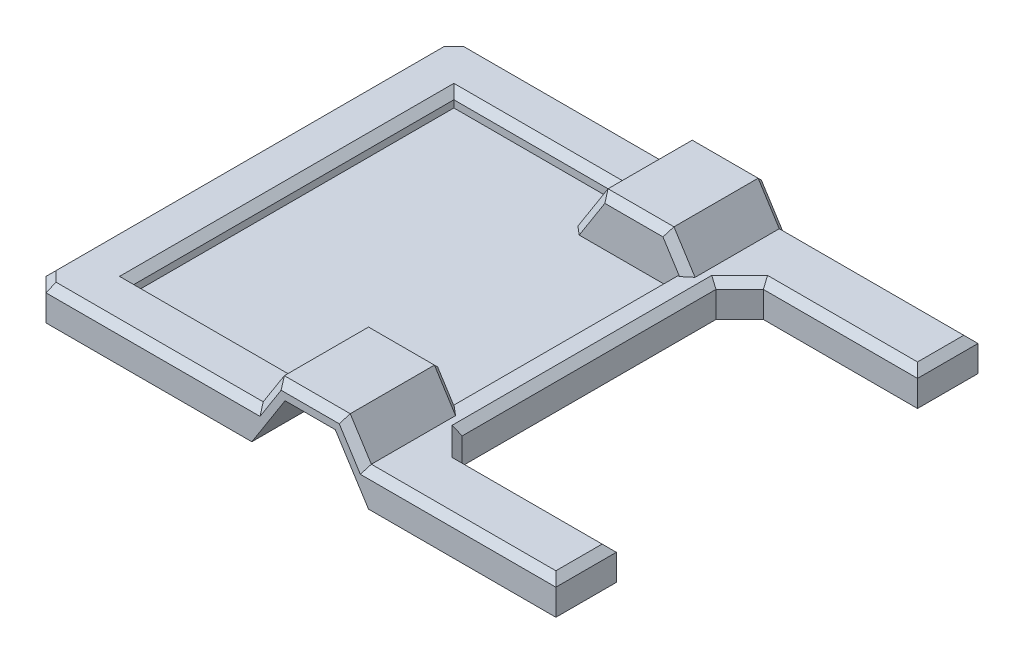
SolidWorks part; units mm, degrees
ref_plane "前视基准面" through (0, 0, 0) normal (0, 0, 1) x (1, 0, 0)
ref_plane "上视基准面" through (0, 0, 0) normal (0, 1, 0) x (1, 0, 0)
ref_plane "右视基准面" through (0, 0, 0) normal (1, 0, 0) x (0, 0, -1)
sketch "草图1" plane through (0, 0, 0) normal (0, 1, 0) x (1, 0, 0)
  line L0 (33.0985, 0) -> (123.5985, 0)
  line L1 (123.5985, 0) -> (123.5985, 67.5)
  line L2 (123.5985, 67.5) -> (33.0985, 67.5)
  line L3 (33.0985, 67.5) -> (33.0985, 0)
extrude "凸台-拉伸1" add sketch "草图1" along normal blind 4
sketch "草图2" plane through (0, 4, 0) normal (0, 1, 0) x (1, 0, 0)
  line L0 (123.5985, 0) -> (123.5985, -10.75)
  line L2 (123.5985, -10.75) -> (94.0985, -10.75)
  line L3 (94.0985, -10.75) -> (94.0985, 0)
  line L4 (33.0985, 0) -> (123.5985, 0) construction
  line L5 (94.0985, 0) -> (123.5985, 0)
  line L6 (33.0985, 0) -> (69.4985, 0)
  line L7 (94.0985, 67.5) -> (123.5985, 67.5)
  line L8 (94.0985, 78.25) -> (94.0985, 67.5)
  line L9 (123.5985, 78.25) -> (94.0985, 78.25)
  line L10 (123.5985, 67.5) -> (123.5985, 78.25)
  line L11 (69.4985, 0) -> (69.4985, -10.75)
  line L12 (69.4985, -10.75) -> (33.0985, -10.75)
  line L13 (33.0985, -10.75) -> (33.0985, 0)
  line L14 (33.0985, 67.5) -> (69.4985, 67.5)
  line L15 (123.5985, 67.5) -> (33.0985, 67.5) construction
  line L16 (69.4985, 67.5) -> (69.4985, 78.25)
  line L17 (69.4985, 78.25) -> (33.0985, 78.25)
  line L18 (33.0985, 78.25) -> (33.0985, 67.5)
extrude "凸台-拉伸2" add sketch "草图2" against normal blind 4
sketch "草图3" plane through (0, 4, 0) normal (0, 1, 0) x (1, 0, 0)
  line L0 (69.4985, 67.5) -> (69.4985, 61.5)
  line L1 (69.4985, 61.5) -> (94.0985, 61.5)
  line L2 (94.0985, 61.5) -> (94.0985, 67.5)
  line L3 (94.0985, 67.5) -> (69.4985, 67.5)
  line L4 (69.4985, 0) -> (69.4985, 6)
  line L5 (69.4985, 6) -> (94.0985, 6)
  line L6 (94.0985, 6) -> (94.0985, 0)
  line L7 (94.0985, 0) -> (69.4985, 0)
extrude "切除-拉伸1" cut sketch "草图3" against normal up to surface (4 mm away) up to face at (80.6485, 0, -33.75)
sketch "草图4" plane through (0, 0, -6) normal (0, 0, 1) x (1, 0, 0)
  line L11 (88.7453, 14) -> (95.109, 4)
  line L12 (88.7453, 14) -> (74.8517, 14)
  line L13 (74.8517, 14) -> (68.488, 4)
  line L14 (69.4985, 0) -> (69.4985, 4)
  line L15 (69.4985, 4) -> (68.488, 4)
  line L17 (94.0985, 0) -> (94.0985, 4)
  line L18 (94.0985, 4) -> (95.109, 4)
  line L20 (94.0985, 0) -> (69.4985, 0)
  point P5 (96.6295, 1.6106)
  point P8 (66.9675, 1.6106)
extrude "凸台-拉伸3" add sketch "草图4" against normal blind 4
sketch "草图5" plane through (0, 0, -6) normal (0, 0, 1) x (1, 0, 0)
  line L0 (76.4985, 11) -> (69.4985, 0)
  line L1 (87.0985, 11) -> (76.4985, 11)
  line L2 (69.4985, 0) -> (69.4985, 4)
  line L3 (69.4985, 4) -> (68.488, 4)
  line L4 (87.0985, 11) -> (94.0985, 0)
  line L5 (94.0985, 0) -> (94.0985, 4)
  line L6 (94.0985, 4) -> (95.109, 4)
  line L8 (69.4985, 0) -> (94.0985, 0)
  line L9 (94.0985, 0) -> (94.0985, 4)
  line L10 (94.0985, 4) -> (95.109, 4)
  line L11 (95.109, 4) -> (88.7453, 14)
  line L12 (88.7453, 14) -> (74.8517, 14)
  line L13 (74.8517, 14) -> (68.488, 4)
  line L14 (68.488, 4) -> (69.4985, 4)
  line L15 (69.4985, 4) -> (69.4985, 0)
  line L19 (95.109, 4) -> (88.7453, 14)
  line L20 (88.7453, 14) -> (74.8517, 14)
  line L21 (74.8517, 14) -> (68.488, 4)
  line L24 (92.578, 2.3894) -> (87.0985, 11) construction
  line L25 (76.4985, 11) -> (71.019, 2.3894) construction
  dimension "D1" = 0
extrude "凸台-拉伸4" add sketch "草图5" along normal up to surface (16.75 mm away) up to face at (51.2985, 2, 10.75)
sketch "草图6" plane through (0, 0, -61.5) normal (0, 0, -1) x (-1, 0, 0)
  line L16 (-95.109, 4) -> (-94.0985, 4)
  line L17 (-88.7453, 14) -> (-95.109, 4)
  line L18 (-74.8517, 14) -> (-88.7453, 14)
  line L19 (-68.488, 4) -> (-74.8517, 14)
  line L20 (-69.4985, 4) -> (-68.488, 4)
  line L21 (-69.4985, 0) -> (-69.4985, 4)
  line L22 (-94.0985, 0) -> (-69.4985, 0)
  line L23 (-94.0985, 4) -> (-94.0985, 0)
  line L24 (-95.109, 4) -> (-94.0985, 4)
  line L25 (-88.7453, 14) -> (-95.109, 4)
  line L26 (-74.8517, 14) -> (-88.7453, 14)
  line L27 (-68.488, 4) -> (-74.8517, 14)
  line L28 (-69.4985, 4) -> (-68.488, 4)
  line L29 (-69.4985, 0) -> (-69.4985, 4)
  line L30 (-94.0985, 0) -> (-69.4985, 0)
  line L31 (-94.0985, 4) -> (-94.0985, 0)
  dimension "D1" = 0
extrude "凸台-拉伸5" add sketch "草图6" against normal blind 4
sketch "草图7" plane through (0, 0, -61.5) normal (0, 0, -1) x (-1, 0, 0)
  line L26 (-95.109, 4) -> (-94.0985, 4)
  line L27 (-88.7453, 14) -> (-95.109, 4)
  line L28 (-74.8517, 14) -> (-88.7453, 14)
  line L29 (-68.488, 4) -> (-74.8517, 14)
  line L30 (-69.4985, 4) -> (-68.488, 4)
  line L31 (-69.4985, 0) -> (-69.4985, 4)
  line L32 (-76.4985, 11) -> (-69.4985, 0)
  line L33 (-87.0985, 11) -> (-76.4985, 11)
  line L34 (-94.0985, 0) -> (-87.0985, 11)
  line L35 (-94.0985, 4) -> (-94.0985, 0)
  line L36 (-95.109, 4) -> (-94.0985, 4)
  line L37 (-88.7453, 14) -> (-95.109, 4)
  line L38 (-74.8517, 14) -> (-88.7453, 14)
  line L39 (-68.488, 4) -> (-74.8517, 14)
  line L40 (-69.4985, 4) -> (-68.488, 4)
  line L41 (-69.4985, 0) -> (-69.4985, 4)
  line L42 (-76.4985, 11) -> (-69.4985, 0)
  line L43 (-87.0985, 11) -> (-76.4985, 11)
  line L44 (-94.0985, 0) -> (-87.0985, 11)
  line L45 (-94.0985, 4) -> (-94.0985, 0)
  dimension "D1" = 0
extrude "凸台-拉伸6" add sketch "草图7" along normal up to surface (16.75 mm away) up to face at (108.8485, 2, -78.25)
sketch "草图8" plane through (0, 4, 0) normal (0, 1, 0) x (1, 0, 0)
  line L0 (123.5985, -10.75) -> (123.5985, 0)
  line L1 (123.5985, -10.75) -> (123.5985, 78.25) construction
  line L2 (123.5985, 0) -> (133.5985, 0)
  line L3 (133.5985, 0) -> (133.5985, -10.75)
  line L4 (133.5985, -10.75) -> (123.5985, -10.75)
  line L6 (133.5985, 78.25) -> (123.5985, 78.25)
  line L7 (133.5985, 67.5) -> (133.5985, 78.25)
  line L8 (123.5985, 67.5) -> (133.5985, 67.5)
  line L9 (123.5985, 78.25) -> (123.5985, 67.5)
extrude "凸台-拉伸7" add sketch "草图8" against normal blind 4
sketch "草图9" plane through (33.0985, 0, 0) normal (-1, 0, 0) x (0, 0, 1)
  line L4 (-78.25, 0) -> (10.75, 0)
  line L5 (10.75, 0) -> (10.75, 4)
  line L6 (10.75, 4) -> (-78.25, 4)
  line L7 (-78.25, 4) -> (-78.25, 0)
  line L8 (-78.25, 0) -> (10.75, 0)
  line L9 (10.75, 0) -> (10.75, 4)
  line L10 (10.75, 4) -> (-78.25, 4)
  line L11 (-78.25, 4) -> (-78.25, 0)
  dimension "D1" = 0
extrude "凸台-拉伸8" add sketch "草图9" along normal blind 10
chamfer "倒角2" distance 3 angle 45 2 edges at (23.0985, 2, -78.25) (23.0985, 2, 10.75)
ref_plane "基准面4" through (0, 7, 0) normal (0, 1, 0) x (1, 0, 0)
sketch "草图10" plane through (0, 7, 0) normal (0, 1, 0) x (1, 0, 0)
  line L2 (88.7453, 78.25) -> (95.109, 78.25) construction
  line L4 (133.5985, 78.25) -> (95.109, 78.25) construction
  line L5 (133.5985, 67.5) -> (133.5985, 78.25) construction
  line L6 (123.5985, 67.5) -> (133.5985, 67.5) construction
  line L13 (68.488, 78.25) -> (26.0985, 78.25) construction
  line L14 (26.0985, 78.25) -> (23.0985, 75.25) construction
  line L17 (92.8282, 78.25) -> (95.109, 78.25)
  line L18 (70.7621, 78.25) -> (68.488, 78.25)
  line L19 (133.5985, 78.25) -> (95.109, 78.25)
  line L20 (133.5985, 67.5) -> (133.5985, 78.25)
  line L21 (123.5985, 67.5) -> (133.5985, 67.5)
  line L25 (23.0985, -7.75) -> (23.0985, 75.25)
  line L28 (68.488, 78.25) -> (26.0985, 78.25)
  line L29 (26.0985, 78.25) -> (23.0985, 75.25)
  line L32 (23.0985, -7.75) -> (23.0985, 75.25) construction
  line L33 (123.5985, 67.5) -> (92.8282, 67.5)
  line L42 (70.7621, 78.25) -> (70.7621, 67.5)
  line L43 (92.8282, 78.25) -> (92.8282, 67.5)
  line L44 (70.7621, 67.5) -> (33.8485, 67.5)
  line L47 (33.8485, 0) -> (33.8485, 67.5)
  line L48 (70.7621, 0) -> (33.8485, 0)
  line L49 (92.8282, -10.75) -> (92.8282, 0)
  line L50 (70.7621, -10.75) -> (70.7621, 0)
  line L51 (123.5985, 0) -> (92.8282, 0)
  line L52 (26.0985, -10.75) -> (23.0985, -7.75)
  line L53 (68.488, -10.75) -> (26.0985, -10.75)
  line L54 (123.5985, 0) -> (133.5985, 0)
  line L55 (133.5985, 0) -> (133.5985, -10.75)
  line L56 (133.5985, -10.75) -> (95.109, -10.75)
  line L57 (70.7621, -10.75) -> (68.488, -10.75)
  line L58 (92.8282, -10.75) -> (95.109, -10.75)
  point P16 (33.8485, 33.75)
  point P30 (23.0985, 33.75)
extrude "凸台-拉伸9" add sketch "草图10" against normal up to next
sketch "草图11" plane through (0, 4, 0) normal (0, 1, 0) x (1, 0, 0)
  line L2 (96.0985, 0) -> (96.0985, 67.5)
  line L3 (95.109, 67.5) -> (123.5985, 67.5) construction
  line L4 (96.0985, 67.5) -> (123.5985, 67.5)
  line L5 (123.5985, 67.5) -> (123.5985, 0)
  line L6 (96.0985, 0) -> (123.5985, 0)
extrude "切除-拉伸2" cut sketch "草图11" against normal through all
sketch "草图12" plane through (0, 0, -67.5) normal (0, 0, 1) x (1, 0, 0)
  line L0 (96.0985, 4) -> (96.0985, 7)
  line L1 (93.1999, 7) -> (133.5985, 7) construction
  line L2 (96.0985, 7) -> (93.1999, 7)
  line L3 (93.1999, 7) -> (93.1999, 4)
  line L4 (93.1999, 4) -> (96.0985, 4)
extrude "凸台-拉伸10" add sketch "草图12" along normal up to next
sketch "草图13" plane through (0, 0, -57.5) normal (0, 0, 1) x (1, 0, 0)
  line L2 (93.1999, 7) -> (91.0985, 7)
  line L4 (93.1999, 4) -> (68.488, 4) construction
  line L5 (91.0985, 4) -> (93.1999, 4)
  line L6 (93.1999, 4) -> (93.1999, 7) construction
  line L7 (93.1999, 4) -> (93.1999, 7)
  line L10 (91.0985, 7) -> (89.1894, 4)
  line L11 (91.0985, 4) -> (89.1894, 4)
extrude "凸台-拉伸11" add sketch "草图13" along normal up to next
sketch "草图14" plane through (0, 0, -67.5) normal (0, 0, 1) x (1, 0, 0)
  line L4 (133.5985, 7) -> (96.0985, 7)
  line L5 (96.0985, 7) -> (96.0985, 0)
  line L6 (96.0985, 0) -> (133.5985, 0)
  line L7 (133.5985, 0) -> (133.5985, 7)
  line L8 (133.5985, 7) -> (96.0985, 7)
  line L9 (96.0985, 7) -> (96.0985, 0)
  line L10 (96.0985, 0) -> (133.5985, 0)
  line L11 (133.5985, 0) -> (133.5985, 7)
  dimension "D1" = 0
extrude "凸台-拉伸12" add sketch "草图14" along normal blind 2
sketch "草图15" plane through (0, 0, 0) normal (0, 0, -1) x (-1, 0, 0)
  line L4 (-96.0985, 0) -> (-96.0985, 7)
  line L5 (-96.0985, 7) -> (-133.5985, 7)
  line L6 (-133.5985, 7) -> (-133.5985, 0)
  line L7 (-133.5985, 0) -> (-96.0985, 0)
  line L8 (-96.0985, 0) -> (-96.0985, 7)
  line L9 (-96.0985, 7) -> (-133.5985, 7)
  line L10 (-133.5985, 7) -> (-133.5985, 0)
  line L11 (-133.5985, 0) -> (-96.0985, 0)
  dimension "D1" = 0
extrude "凸台-拉伸13" add sketch "草图15" along normal blind 2
chamfer "倒角3" distance 5 angle 45 2 edges at (96.0985, 3.5, -2) (96.0985, 3.5, -65.5)
chamfer "倒角4" distance 1.5 angle 45 29 edges at (133.5985, 7, 4.375) (133.5985, 7, -71.875) (113.3992, 7, -78.25) (90.9726, 10.5, -78.25) (81.7985, 14, -78.25) (72.6244, 10.5, -78.25) (48.2478, 7, -78.25) (24.5985, 7, -76.75) (23.0985, 7, -33.75) (24.5985, 7, 9.25) (113.3992, 7, 10.75) (90.9726, 10.5, 10.75) (81.7985, 14, 10.75) (72.6244, 10.5, 10.75) (48.2478, 7, 10.75) (117.3485, 7, -2) (98.5985, 7, -4.5) (96.0985, 7, -33.75) (98.5985, 7, -63) (117.3485, 7, -65.5) (90.9726, 10.5, -10) (81.7985, 14, -10) (71.6699, 9, -10) (52.1228, 7, 0) (33.8485, 7, -33.75) (52.1228, 7, -67.5) (71.6699, 9, -57.5) (81.7985, 14, -57.5) (90.9726, 10.5, -57.5)
